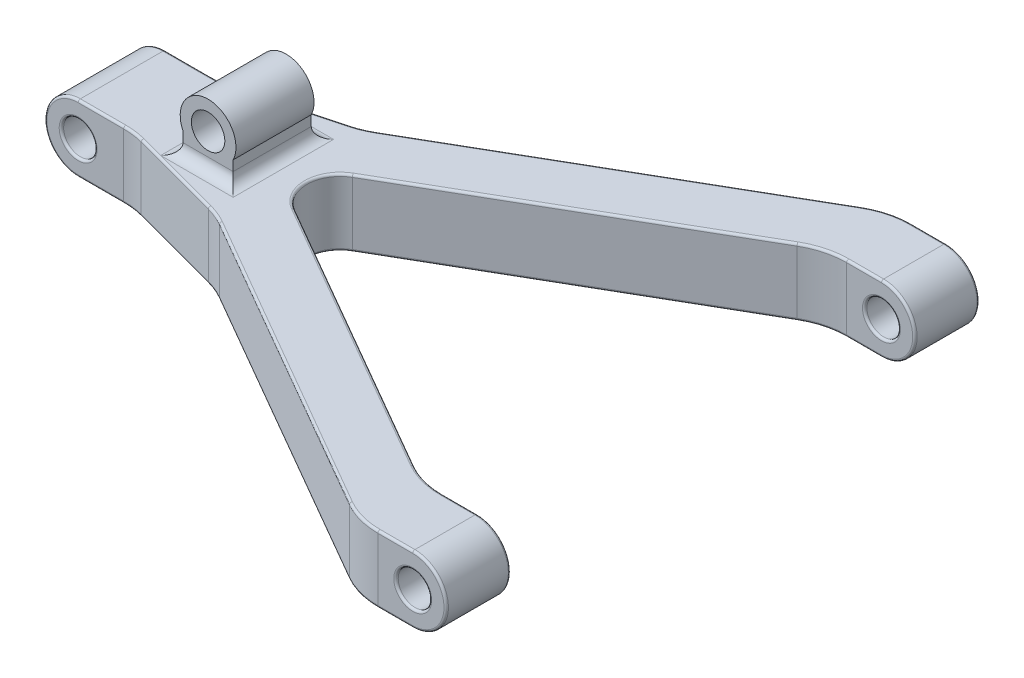
SolidWorks part; units mm, degrees
ref_plane "Alzado" through (0, 0, 0) normal (0, 0, 1) x (1, 0, 0)
ref_plane "Planta" through (0, 0, 0) normal (0, 1, 0) x (1, 0, 0)
ref_plane "Vista lateral" through (0, 0, 0) normal (1, 0, 0) x (0, 0, -1)
sketch "Croquis1" plane through (0, 0, 0) normal (0, 1, 0) x (1, 0, 0)
  line L0 (0, 0) -> (159.219, 0) construction
  line L1 (-194.7399, -39) -> (-194.7399, 39)
  line L2 (-194.7399, 39) -> (-144.7399, 39)
  line L3 (-144.7399, 39) -> (-44.7399, 65.7949)
  line L4 (-44.7399, 65.7949) -> (255.2601, 239)
  line L5 (255.2601, 239) -> (305.2601, 239)
  line L6 (255.2601, -239) -> (305.2601, -239)
  line L7 (-44.7399, -65.7949) -> (255.2601, -239)
  line L8 (-144.7399, -39) -> (-44.7399, -65.7949)
  line L9 (-194.7399, -39) -> (-144.7399, -39)
  line L10 (305.2601, 239) -> (305.2601, 181.26)
  line L11 (305.2601, 181.26) -> (255.2515, 181.26)
  line L12 (255.2515, 181.26) -> (-13.7, 25.9808)
  line L13 (-13.7, -25.9808) -> (255.2515, -181.26)
  line L14 (255.2515, -181.26) -> (305.2601, -181.26)
  line L15 (305.2601, -181.26) -> (305.2601, -239)
  arc A0 (-13.7, 25.9808) -> (-13.7, -25.9808) centre (1.3, 0) ccw
  point P17 (-194.7399, 0)
  point P21 (0, 0)
  dimension "D10" = 30
  dimension "D1" = 39
  dimension "D2" = 500
  dimension "D3" = 50
  dimension "D4" = 100
  dimension "D5" = 300
  dimension "D6" = 165
  dimension "D7" = 165
  dimension "D8" = 57.74
  dimension "D9" = 50
  dimension "D11" = 1.3
extrude "Saliente-Extruir1" add sketch "Croquis1" along normal blind 60 contours L15 L6 L7 L8 L9 L1 L2 L3 L4 L5 L10 L11 L12 A0 L13 L14
sketch "Croquis2" plane through (0, 0, 39) normal (0, 0, 1) x (1, 0, 0)
  line L0 (-194.7399, 60) -> (-194.7399, 0) construction
  circle A0 centre (-194.7399, 30) radius 30
extrude "Saliente-Extruir2" add sketch "Croquis2" against normal up to surface (78 mm away) up to face at (-169.7399, 30, -39)
sketch "Croquis3" plane through (0, 0, 39) normal (0, 0, 1) x (1, 0, 0)
  circle A0 centre (-194.7399, 30) radius 15
  dimension "D1" = 30
extrude "Cortar-Extruir1" cut sketch "Croquis3" against normal up to next
sketch "Croquis4" plane through (0, 0, 239) normal (0, 0, 1) x (1, 0, 0)
  line L0 (305.2601, 60) -> (305.2601, 0) construction
  circle A0 centre (305.2601, 30) radius 30
extrude "Saliente-Extruir3" add sketch "Croquis4" against normal up to surface (57.74 mm away) up to face at (280.2558, 30, 181.26)
sketch "Croquis5" plane through (0, 0, -239) normal (0, 0, -1) x (-1, 0, 0)
  line L0 (-305.2601, 60) -> (-305.2601, 0) construction
  circle A0 centre (-305.2601, 30) radius 30
extrude "Saliente-Extruir4" add sketch "Croquis5" against normal up to surface (57.74 mm away) up to face at (280.2558, 30, -181.26)
sketch "Croquis6" plane through (0, 0, 239) normal (0, 0, 1) x (1, 0, 0)
  circle A0 centre (305.2601, 30) radius 15
  dimension "D1" = 30
extrude "Cortar-Extruir2" cut sketch "Croquis6" against normal through all both and the other way through all
fillet "Redondeo1" radius 70 8 edges at (-44.7399, 30, 65.7949) (-144.7399, 30, 39) (-144.7399, 30, -39) (-44.7399, 30, -65.7949) (255.2601, 30, -239) (255.2515, 30, -181.26) (255.2515, 30, 181.26) (255.2601, 30, 239)
fillet "Redondeo2" radius 2 54 edges at (335.2601, 30, -181.26) (289.6341, 0, -181.26) (255.8906, 0, -178.8748) (112.654, 0, -98.9313) (-28.7, 0, 0) (112.654, 0, 98.9313) (255.8906, 0, 178.8748) (289.6341, 0, 181.26) (335.2601, 30, 181.26) (-224.7399, 30, 39) (-174.3477, 0, 39) (-144.8187, 0, 39.5989) (-94.7399, 0, 52.3975) (-44.971, 0, 66.353) (101.1289, 0, 150.0123) (255.8993, 0, 236.6148) (289.6384, 0, 239) (335.2601, 30, 239) (-224.7399, 30, -39) (-174.3477, 0, -39) (-144.8187, 0, -39.5989) (-94.7399, 0, -52.3975) (-44.971, 0, -66.353) (101.1289, 0, -150.0123) (255.8993, 0, -236.6148) (289.6384, 0, -239) (335.2601, 30, -239) (289.6341, 60, -181.26) (255.8906, 60, -178.8748) (112.654, 60, -98.9313) (-28.7, 60, 0) (112.654, 60, 98.9313) (255.8906, 60, 178.8748) (289.6341, 60, 181.26) (289.6384, 60, 239) (255.8993, 60, 236.6148) (101.1289, 60, 150.0123) (-44.971, 60, 66.353) (-94.7399, 60, 52.3975) (-144.8187, 60, 39.5989) (-174.3477, 60, 39) (-174.3477, 60, -39) (-144.8187, 60, -39.5989) (-94.7399, 60, -52.3975) (-44.971, 60, -66.353) (101.1289, 60, -150.0123) (255.8993, 60, -236.6148) (289.6384, 60, -239) (290.2601, 30, 181.26) (320.2601, 30, -181.26) (320.2601, 30, -239) (290.2601, 30, 239) (-179.7399, 30, 39) (-209.7399, 30, -39)
sketch "Croquis7" plane through (0, 60, 0) normal (0, 1, 0) x (1, 0, 0)
  line L0 (-194.7399, -37) -> (-194.7399, 37) construction
  line L1 (-59.7399, -35) -> (-104.7399, -35)
  line L2 (-59.7399, -35) -> (-59.7399, 35)
  line L3 (-59.7399, 35) -> (-104.7399, 35)
  line L4 (-104.7399, -35) -> (-104.7399, 35)
  line L5 (-59.7399, -35) -> (-104.7399, 35) construction
  line L6 (-59.7399, 35) -> (-104.7399, -35) construction
  point P0 (-82.2399, 0)
  point P5 (-59.7399, 0)
  dimension "D1" = 45
  dimension "D2" = 70
  dimension "D3" = 90
extrude "Saliente-Extruir5" add sketch "Croquis7" along normal blind 30
sketch "Croquis8" plane through (0, 0, 35) normal (0, 0, 1) x (1, 0, 0)
  line L0 (-104.7399, 90) -> (-59.7399, 90) construction
  circle A0 centre (-82.2399, 90) radius 25
  dimension "D1" = 50
extrude "Saliente-Extruir6" add sketch "Croquis8" against normal up to surface (70 mm away) up to face at (-82.2399, 75, -35)
sketch "Croquis9" plane through (0, 0, -35) normal (0, 0, -1) x (-1, 0, 0)
  circle A0 centre (82.2399, 90) radius 15
  dimension "D1" = 30
extrude "Cortar-Extruir3" cut sketch "Croquis9" against normal up to next
fillet "Redondeo3" radius 10 4 edges at (-59.7399, 60, 0) (-82.2399, 60, 35) (-82.2399, 60, -35) (-104.7399, 60, 0)
